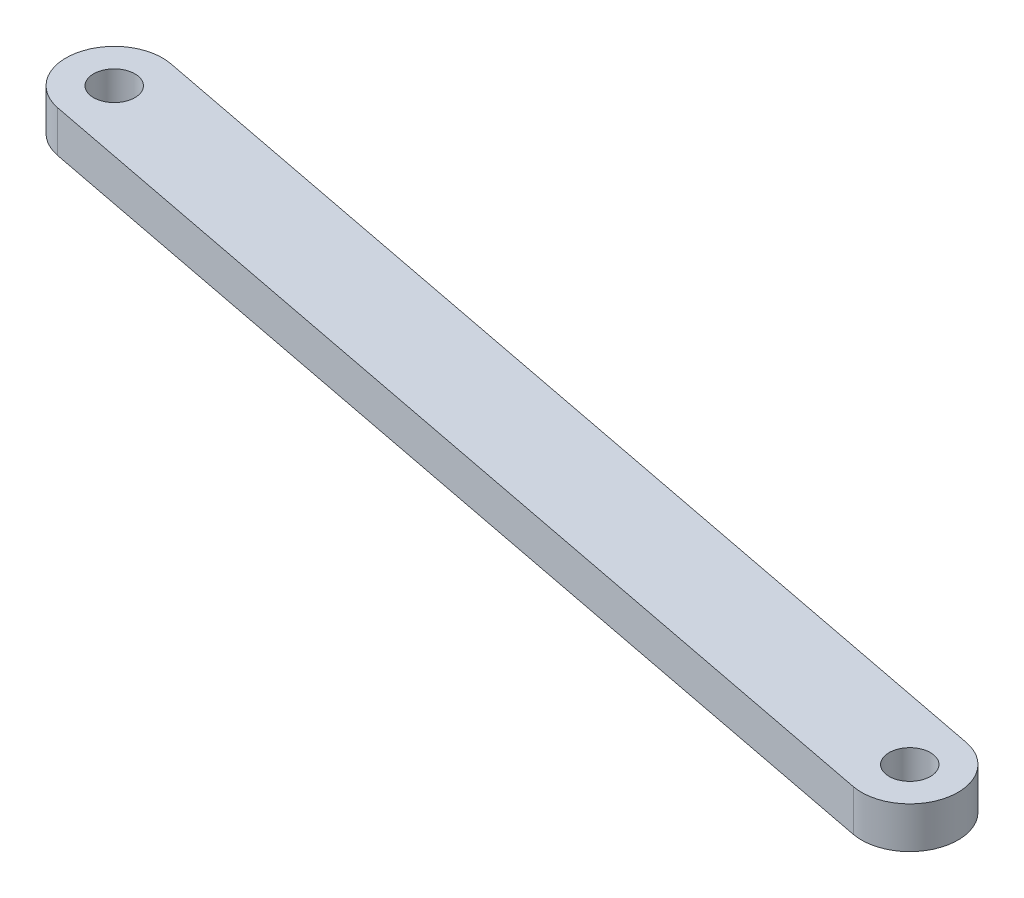
SolidWorks part; units mm, degrees
ref_plane "Front Plane" through (0, 0, 0) normal (0, 0, 1) x (1, 0, 0)
ref_plane "Top Plane" through (0, 0, 0) normal (0, 1, 0) x (1, 0, 0)
ref_plane "Right Plane" through (0, 0, 0) normal (1, 0, 0) x (0, 0, -1)
sketch "Sketch2" plane through (0, 84, 0) normal (0, 1, 0) x (1, 0, 0)
  line L0 (-5, 87.5) -> (-76.5046, 101.2894) construction
  line L1 (-75.8419, 104.7261) -> (-77.1674, 97.8527) construction
  line L2 (-4.3373, 90.9367) -> (-5.6628, 84.0633) construction
  line L3 (-5.6628, 84.0633) -> (-77.1674, 97.8527)
  line L4 (-75.8419, 104.7261) -> (-4.3373, 90.9367)
  circle A0 centre (-5, 87.5) radius 1.5 construction
  circle A1 centre (-76.5046, 101.2894) radius 1.0339 construction
  circle A2 centre (-5, 87.5) radius 1.5
  circle A3 centre (-76.5046, 101.2894) radius 1.0339 construction
  circle A4 centre (-76.5046, 101.2894) radius 1.5
  arc A5 (-77.1674, 97.8527) -> (-75.8419, 104.7261) centre (-76.5046, 101.2894) cw
  arc A6 (-4.3373, 90.9367) -> (-5.6628, 84.0633) centre (-5, 87.5) cw
  point P10 (-76.5046, 101.2894)
  point P13 (-5, 87.5)
  line M7 (39.7825, 110.0118) -> (-6.3498, 90.7293)
  arc M8 (-6.3498, 90.7293) -> (-3.6502, 84.2707) centre (-5, 87.5) ccw
  circle M11 centre (-5, 87.5) radius 1.5
  dimension "D1" = 2
extrude "Boss-Extrude2" add sketch "Sketch2" along normal blind 3 contours A6 L4 M7 M8 M11 | A5 L3 L4 A4 M8 M7 region at (-8.3821, 84, -87.1514) region at (-42.9947, 84, -94.8264)
